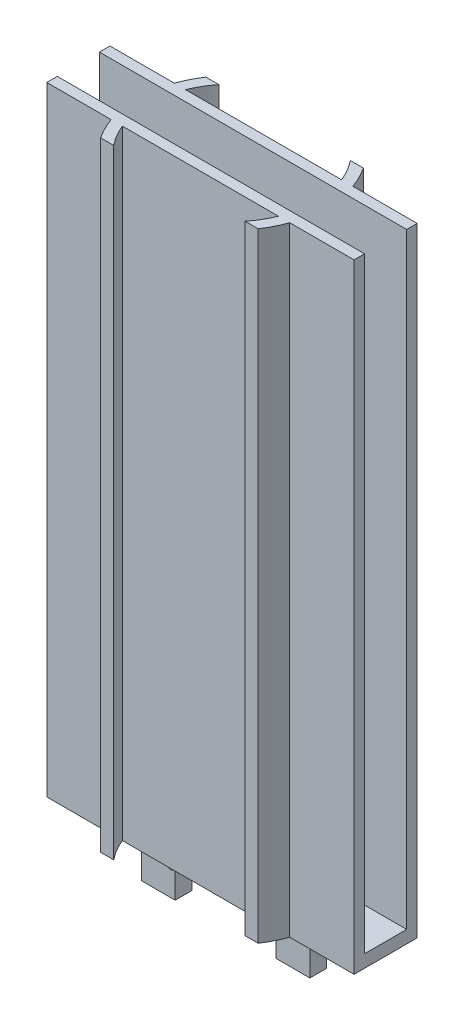
SolidWorks part; units mm, degrees
ref_plane "Front Plane" through (0, 0, 0) normal (0, 0, 1) x (1, 0, 0)
ref_plane "Top Plane" through (0, 0, 0) normal (0, 1, 0) x (1, 0, 0)
ref_plane "Right Plane" through (0, 0, 0) normal (1, 0, 0) x (0, 0, -1)
sketch "Sketch1" plane through (0, 0, 0) normal (0, 1, 0) x (1, 0, 0)
  line L0 (-36.5, 10) -> (-36.5, 0)
  line L1 (0, 0) -> (-73, 0)
  line L2 (0, 0) -> (0, 10)
  line L3 (0, 10) -> (-73, 10)
  line L4 (-73, 0) -> (-73, 10)
  line L5 (-73, 5) -> (0, 5)
  line L6 (-75, 12.5) -> (2, 12.5)
  line L7 (-75, 12.5) -> (-75, -2.5)
  line L8 (-75, -2.5) -> (2, -2.5)
  line L9 (2, 12.5) -> (2, -2.5)
  line L10 (-55.2083, 17.5) -> (-17.7917, 17.5)
  line L11 (-55.2083, -7.5) -> (-17.7917, -7.5)
  line L12 (-73, 10) -> (-73, 12.5)
  line L13 (-73, 0) -> (-73, -2.5)
  line L14 (0, 10) -> (0, 12.5)
  line L15 (0, 0) -> (0, -2.5)
  circle A0 centre (-36.5, 5) radius 24.5
  circle A1 centre (-36.5, 5) radius 22.5
  circle A2 centre (-36.5, 5) radius 20
  dimension "D3" = 49
  dimension "D4" = 45
  dimension "D7" = 40
  dimension "D1" = 10
  dimension "D2" = 73
  dimension "D5" = 15
  dimension "D6" = 7.5
  dimension "D8" = 5
  dimension "D9" = 5
  dimension "D10" = 2
  dimension "D11" = 2
extrude "Boss-Extrude1" add sketch "Sketch1" against normal blind 3 contours A0 L6 L12 L3 | A0 L3 L4 L5 | A0 L5 L4 L1 | A0 L1 L13 L8 | A1 L6 A0 L3 | A1 L3 A0 L5 | A1 L5 A0 L1 | A1 L1 A0 L8 | A2 L6 A1 L3 | A2 L3 A1 L5 | A2 L5 A1 L1 | A2 L1 A1 L8 | L3 A2 L6 | L3 A2 L5 L0 | L5 A2 L1 L0 | L8 A2 L1 | L5 A2 L3 L0 | L1 A2 L5 L0 | A2 L3 A1 L6 | A2 L5 A1 L3 | A2 L1 A1 L5 | A2 L8 A1 L1 | A1 L3 A0 L6 | A1 L5 A0 L3 | A1 L1 A0 L5 | A1 L8 A0 L1 | A0 L3 L14 L6 | A0 L5 L2 L3 | A0 L1 L2 L5 | A0 L8 L15 L1 | A2 L11 A1 L8 | A2 L8 A1 L11 | A2 L10 A1 L6 | A2 L6 A1 L10 region at (-26.6043, 0, -7.4867) region at (-36.5, 0, -11.241) region at (-46.3957, 0, -7.4867) region at (-26.6043, 0, -2.5133) region at (-46.3957, 0, -2.5133) region at (-16.2102, 0, -11.258) region at (-15.45, 0, -7.5119) region at (-57.55, 0, -7.5119) region at (-56.7898, 0, -11.258) region at (-36.5, 0, 1.241) region at (-57.55, 0, -2.4881) region at (-15.45, 0, -2.4881) region at (-13.8622, 0, -11.2564) region at (-13.18, 0, -7.5096) region at (-17.8679, 0, -15.0608) region at (-59.82, 0, -7.5096) region at (-59.1378, 0, -11.2564) region at (-55.1321, 0, -15.0608) region at (-16.2102, 0, 1.258) region at (-56.7898, 0, 1.258) region at (-59.82, 0, -2.4904) region at (-13.18, 0, -2.4904) region at (-6.4126, 0, -11.2607) region at (-6.0865, 0, -7.5176) region at (-66.9135, 0, -7.5176) region at (-66.5874, 0, -11.2607) region at (-13.8622, 0, 1.2564) region at (-17.8679, 0, 5.0608) region at (-59.1378, 0, 1.2564) region at (-55.1321, 0, 5.0608) region at (-66.9135, 0, -2.4824) region at (-6.0865, 0, -2.4824) region at (-6.4126, 0, 1.2607) region at (-66.5874, 0, 1.2607)
extrude "Boss-Extrude2" add sketch "Sketch1<4>" along normal blind 144 contours A0 L6 L12 L3 | A1 L6 A0 L3 | A2 L6 A1 L3 | A2 L10 A1 L6 | L3 A2 L6 | A2 L6 A1 L10 | A2 L3 A1 L6 | A1 L3 A0 L6 | A0 L3 L14 L6 | A0 L1 L13 L8 | A1 L1 A0 L8 | A2 L1 A1 L8 | L8 A2 L1 | A2 L8 A1 L1 | A1 L8 A0 L1 | A0 L8 L15 L1 | A2 L11 A1 L8 | A2 L8 A1 L11 region at (-36.5, 0, -11.241) region at (-16.2102, 0, -11.258) region at (-56.7898, 0, -11.258) region at (-36.5, 0, 1.241) region at (-13.8622, 0, -11.2564) region at (-17.8679, 0, -15.0608) region at (-59.1378, 0, -11.2564) region at (-55.1321, 0, -15.0608) region at (-16.2102, 0, 1.258) region at (-56.7898, 0, 1.258) region at (-6.4126, 0, -11.2607) region at (-66.5874, 0, -11.2607) region at (-13.8622, 0, 1.2564) region at (-17.8679, 0, 5.0608) region at (-59.1378, 0, 1.2564) region at (-55.1321, 0, 5.0608) region at (-6.4126, 0, 1.2607) region at (-66.5874, 0, 1.2607)
sketch "Sketch1<4>" plane through (0, 0, 0) normal (0, 1, 0) x (1, 0, 0) same geometry as "Sketch1"
sketch "Sketch2" plane through (0, -3, 0) normal (0, -1, 0) x (1, 0, 0)
  line L0 (-73, -5) -> (0, -5)
  line L1 (-73, 2.5) -> (-73, -12.5) construction
  line L2 (0, 2.5) -> (0, -12.5) construction
  line L3 (-36.5, -5) -> (-36.5, 20.5006)
  line L4 (-52.5, 5.5) -> (-20.5, 5.5)
  line L5 (-52.5, 5.5) -> (-52.5, -18.5)
  line L6 (-52.5, -18.5) -> (-20.5, -18.5)
  line L7 (-20.5, 5.5) -> (-20.5, -18.5)
  line L8 (-52.5, -3.5) -> (-20.5, -3.5)
  line L9 (-20.5, -3.5) -> (-20.5, -1.5)
  line L10 (-20.5, -1.5) -> (-52.5, -1.5)
  line L11 (-20.5, 1.15) -> (-52.5, 1.15)
  line L12 (-55.0405, 2.5) -> (-17.9595, 2.5) construction
  line L13 (-48.5, -3.5) -> (-48.5, -7.5)
  line L14 (-48.5, -7.5) -> (-52.5, -7.5)
  line L15 (-24.5, -3.5) -> (-24.5, -7.5)
  line L16 (-24.5, -7.5) -> (-20.5, -7.5)
  line L18 (-52.5, -3.5) -> (-56.5, -3.5)
  line L19 (-52.5, -3.5) -> (-52.5, -7.5)
  line L20 (-52.5, -7.5) -> (-56.5, -7.5)
  line L21 (-56.5, -3.5) -> (-56.5, -7.5)
  line L22 (-20.5, -3.5) -> (-16.5, -3.5)
  line L23 (-20.5, -3.5) -> (-20.5, -7.5)
  line L24 (-20.5, -7.5) -> (-16.5, -7.5)
  line L25 (-16.5, -3.5) -> (-16.5, -7.5)
  circle A0 centre (-36.5, -5) radius 22.5
  dimension "D1" = 24
  dimension "D2" = 32
  dimension "D3" = 16
  dimension "D4" = 2
  dimension "D5" = 15
  dimension "D6" = 19.65
  dimension "D7" = 21
  dimension "D8" = 4
  dimension "D9" = 4
  dimension "D10" = 4
  dimension "D11" = 4
  dimension "D12" = 4
  dimension "D13" = 4
extrude "Boss-Extrude3" add sketch "Sketch2" along normal blind 12 contours L0 L21 L20 L5 | L18 L21 L0 L5 | L13 L8 L5 L0 | L14 L13 L0 L5 | L15 L16 L7 L0 | L8 L15 L0 L7 | L25 L22 L7 L0 | L25 L0 L7 L24 region at (-54.5, -3, -4.25) region at (-54.5, -3, -6.25) region at (-50.5, -3, -4.25) region at (-50.5, -3, -6.25) region at (-18.5, -3, -6.25) region at (-18.5, -3, -4.25) region at (-22.5, -3, -6.25) region at (-22.5, -3, -4.25)
sketch "Sketch3" plane through (0, 0, -7.5) normal (0, 0, -1) x (-1, 0, 0)
  line L0 (24.5, -3) -> (16.5, -3) construction
  line L1 (48.5, -3) -> (56.5, -3) construction
  line L2 (36.5, -3) -> (36.5, -15.8284)
  line L3 (55.0405, -3) -> (17.9595, -3) construction
  circle A0 centre (23.5, -8.5) radius 0.75
  circle A1 centre (49.5, -8.5) radius 0.75
  point P12 (0, 0)
  dimension "D3" = 1.5
  dimension "D4" = 1.5
  dimension "D1" = 5.5
  dimension "D2" = 5.5
  dimension "D5" = 26
  dimension "D6" = 13
extrude "Cut-Extrude1" cut sketch "Sketch3" against normal through all contours A0 | A1 region at (-23.5, -8.5, -7.5) region at (-49.5, -8.5, -7.5)
